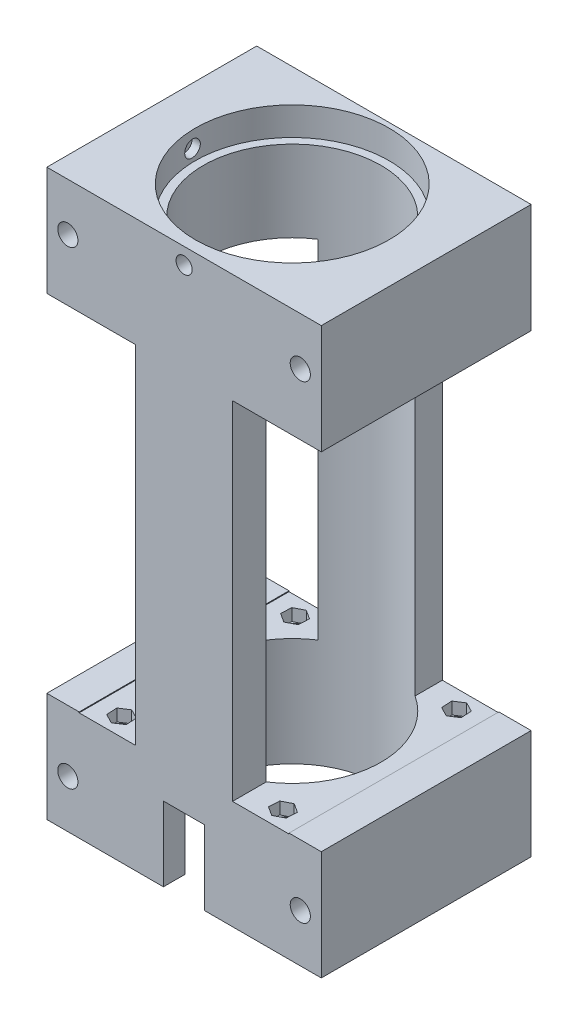
SolidWorks part; units mm, degrees
ref_plane "Front" through (0, 0, 0) normal (0, 0, 1) x (1, 0, 0)
ref_plane "Top" through (0, 0, 0) normal (0, 1, 0) x (1, 0, 0)
ref_plane "Right" through (0, 0, 0) normal (1, 0, 0) x (0, 0, -1)
sketch "草图1" plane through (0, 0, 0) normal (0, 0, 1) x (1, 0, 0)
  line L0 (-100, -70) -> (100, -70) construction
  line L1 (26, 70) -> (-26, 70)
  line L2 (26, 70) -> (26, -70)
  line L3 (26, -70) -> (-26, -70)
  line L4 (-26, 70) -> (-26, -70)
  line L5 (26, 70) -> (-26, -70) construction
  line L6 (26, -70) -> (-26, 70) construction
  point P0 (0, 0)
  dimension "D1" = 52
extrude "凸台-拉伸1" add sketch "草图1" along normal blind 52
sketch "草图2" plane through (0, 70, 0) normal (0, 1, 0) x (1, 0, 0)
  line L0 (26, 0) -> (-26, 0) construction
  circle A0 centre (0, -25.2) radius 22
  dimension "D1" = 44
  dimension "D2" = 25.2
extrude "切除-拉伸1" cut sketch "草图2" against normal through all contours A0
sketch "草图3" plane through (0, 0, 52) normal (0, 0, 1) x (1, 0, 0)
  line L1 (26, -70) -> (26, 70) construction
  line L3 (26, -43.1) -> (26, 42.9)
  line L4 (26, -43.1) -> (12, -43.1)
  line L5 (12, -43.1) -> (12, 42.9)
  line L6 (12, 42.9) -> (26, 42.9)
  line L7 (-26, -70) -> (26, -70) construction
  point P0 (19, -43.1)
  dimension "D1" = 86
  dimension "D2" = 26.9
  dimension "D3" = 14
extrude "切除-拉伸2" cut sketch "草图3" against normal up to surface (52 mm away)
mirror "镜向1" about plane through (0, 0, 0) normal (1, 0, 0) of "切除-拉伸2"
sketch "草图4" plane through (0, 70, 0) normal (0, 1, 0) x (1, 0, 0)
  circle A0 centre (0, -25.2) radius 24
  dimension "D1" = 48
extrude "切除-拉伸3" cut sketch "草图4" against normal blind 7
sketch "草图5" plane through (26, 0, 0) normal (1, 0, 0) x (0, 0, -1)
  line L0 (-52, 70) -> (0, 70) construction
  circle A0 centre (-26, 66) radius 2
  point P5 (-26, 70)
  dimension "D1" = 4
  dimension "D2" = 4
extrude "切除-拉伸4" cut sketch "草图5" against normal through all
sketch "草图6" plane through (0, 0, 52) normal (0, 0, 1) x (1, 0, 0)
  line L0 (26, 70) -> (-26, 70) construction
  circle A0 centre (0, 66) radius 2
  dimension "D1" = 4
  dimension "D2" = 4
extrude "切除-拉伸5" cut sketch "草图6" against normal blind 20
sketch "草图7" plane through (0, -43.1, 0) normal (0, 1, 0) x (1, 0, 0)
  line L0 (-12, -52) -> (-26, -52) construction
  line L1 (-22.3629, -46.2876) -> (-22.2314, -48.9402)
  line L2 (-22.2314, -48.9402) -> (-19.8685, -50.1526)
  line L3 (-19.8685, -50.1526) -> (-17.6371, -48.7124)
  line L4 (-17.6371, -48.7124) -> (-17.7686, -46.0598)
  line L5 (-17.7686, -46.0598) -> (-20.1315, -44.8474)
  line L6 (-20.1315, -44.8474) -> (-22.3629, -46.2876)
  line L7 (-26, 0) -> (-26, -52) construction
  circle A0 centre (-20, -47.5) radius 2.3 construction
  dimension "D1" = 4.6
  dimension "D2" = 4.5
  dimension "D3" = 6
extrude "切除-拉伸6" cut sketch "草图7" against normal blind 3
sketch "草图8" plane through (0, -46.1, 0) normal (0, 1, 0) x (1, 0, 0)
  line L0 (-26, 0) -> (-26, -52) construction
  line L1 (-12, -52) -> (-26, -52) construction
  circle A0 centre (-20, -47.5) radius 2.05
  dimension "D1" = 4.1
  dimension "D2" = 6
  dimension "D3" = 4.5
extrude "切除-拉伸7" cut sketch "草图8" against normal through all
mirror "镜向2" about plane through (0, 0, 0) normal (1, 0, 0) of "切除-拉伸6", "切除-拉伸7"
ref_plane "基准面2" through (0, 0, 26) normal (0, 0, 1) x (1, 0, 0)
mirror "镜向3" about plane through (0, 0, 26) normal (0, 0, 1) of "镜向2"
sketch "草图9" plane through (0, 0, 52) normal (0, 0, 1) x (1, 0, 0)
  line L0 (-26, 70) -> (-26, 42.9) construction
  line L1 (26, 42.9) -> (26, 70) construction
  line L2 (-26, 70) -> (-26, 42.9)
  line L3 (26, 42.9) -> (26, 70)
  line L4 (26, 42.9) -> (34, 42.9)
  line L5 (34, 42.9) -> (34, 70)
  line L6 (34, 70) -> (26, 70)
  line L7 (-26, 42.9) -> (-34, 42.9)
  line L8 (-34, 42.9) -> (-34, 70)
  line L9 (-34, 70) -> (-26, 70)
  dimension "D1" = 8
extrude "凸台-拉伸2" add sketch "草图9" against normal up to surface (52 mm away)
sketch "草图10" plane through (0, 0, 52) normal (0, 0, 1) x (1, 0, 0)
  line L0 (-34, 70) -> (-34, 42.9) construction
  line L1 (34, 42.9) -> (34, 70) construction
  circle A0 centre (28.8, 58.1086) radius 2.5
  circle A1 centre (-28.8, 58.1086) radius 2.5
  point P8 (0, 0)
  dimension "D1" = 5
  dimension "D2" = 5
  dimension "D3" = 5.2
  dimension "D4" = 5.2
extrude "切除-拉伸8" cut sketch "草图10" against normal through all
ref_plane "基准面3" through (0, 0, 0) normal (0, 1, 0) x (1, 0, 0)
mirror "镜向4" about plane through (0, 0, 0) normal (0, 1, 0) of "切除-拉伸8", "凸台-拉伸2"
sketch "草图11" plane through (0, 0, 52) normal (0, 0, 1) x (1, 0, 0)
  line L0 (-34, -70) -> (34, -70) construction
  line L1 (-5.1222, -70) -> (5, -70)
  line L2 (5, -70) -> (5, -51.5841)
  line L3 (5, -51.5841) -> (-5.1222, -51.5841)
  line L4 (-5.1222, -51.5841) -> (-5.1222, -70)
extrude "切除-拉伸9" cut sketch "草图11" against normal blind 10
